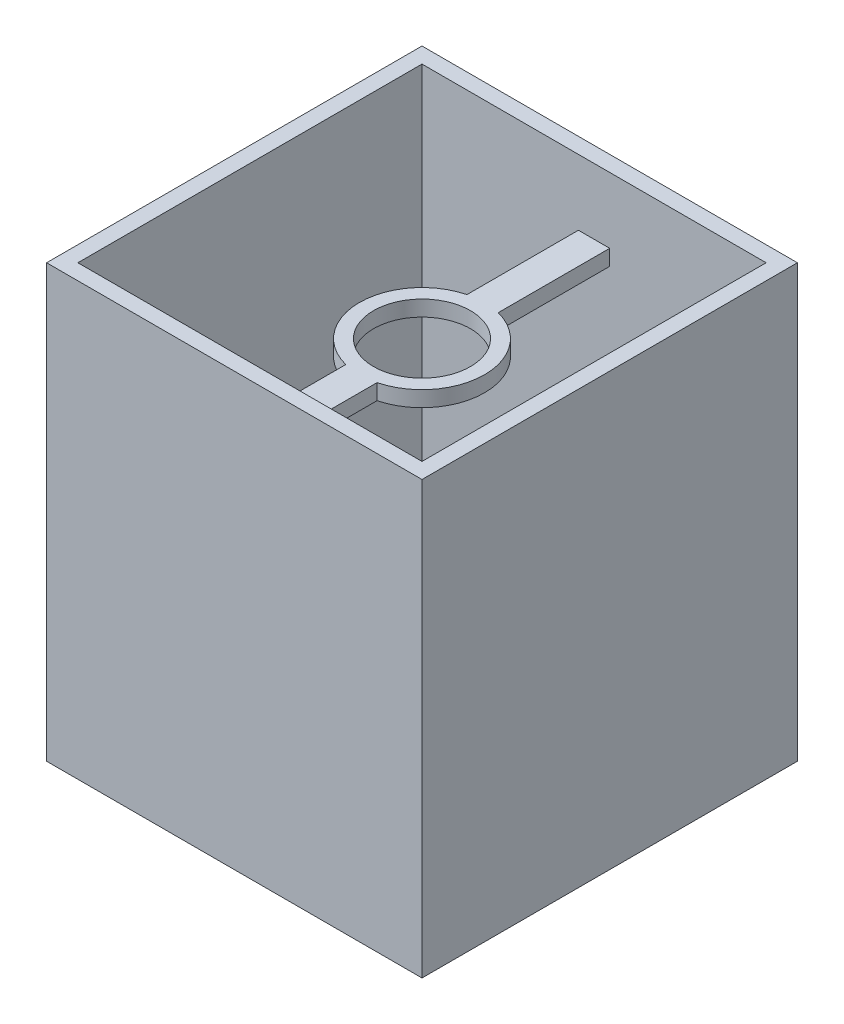
SolidWorks part; units mm, degrees
material "ABS"
ref_plane "Front Plane" through (0, 0, 0) normal (0, 0, 1) x (1, 0, 0)
ref_plane "Top Plane" through (0, 0, 0) normal (0, 1, 0) x (1, 0, 0)
ref_plane "Right Plane" through (0, 0, 0) normal (1, 0, 0) x (0, 0, -1)
sketch "Sketch1" plane through (0, 0, 0) normal (0, 1, 0) x (1, 0, 0)
  line L1 (30, -30) -> (-30, -30)
  line L2 (30, -30) -> (30, 30)
  line L3 (30, 30) -> (-30, 30)
  line L4 (-30, -30) -> (-30, 30)
  line L5 (30, -30) -> (-30, 30) construction
  line L6 (30, 30) -> (-30, -30) construction
  point P0 (0, 0)
  dimension "D1" = 60
  dimension "D2" = 60
extrude "Boss-Extrude1" add sketch "Sketch1" along normal blind 69
sketch "Sketch2" plane through (0, 69, 0) normal (0, 1, 0) x (1, 0, 0)
  line L1 (27.5, -27.5) -> (-27.5, -27.5)
  line L2 (27.5, -27.5) -> (27.5, 27.5)
  line L3 (27.5, 27.5) -> (-27.5, 27.5)
  line L4 (-27.5, -27.5) -> (-27.5, 27.5)
  line L5 (27.5, -27.5) -> (-27.5, 27.5) construction
  line L6 (27.5, 27.5) -> (-27.5, -27.5) construction
  point P0 (0, 0)
  dimension "D1" = 55
  dimension "D2" = 55
extrude "Cut-Extrude1" cut sketch "Sketch2" against normal blind 66.5
sketch "shaft axis" plane through (0, 0, 0) normal (0, 0, 1) x (1, 0, 0)
  line L1 (0, 2.5) -> (0, 81.7337)
  line L2 (27.5, 2.5) -> (-27.5, 2.5) construction
sketch "motor axis" plane through (0, 0, 0) normal (0, 0, 1) x (1, 0, 0)
  line L0 (3.5, 2.5) -> (3.5, 81.7337)
  line L1 (27.5, 2.5) -> (-27.5, 2.5) construction
  line L2 (0, 2.5) -> (0, 81.7337) construction
  dimension "D1" = 3.5
sketch "Sketch3" plane through (0, 2.5, 0) normal (0, 1, 0) x (1, 0, 0)
  line L0 (-27.5, -27.5) -> (27.5, -27.5) construction
  circle A0 centre (16.36, 2.5) radius 1.5
  circle A1 centre (16.36, -2.5) radius 1.5
  point P0 (16.36, 2.5)
  point P2 (16.36, -2.5)
  dimension "D1" = 25
  dimension "D2" = 5
  dimension "D3" = 3
  dimension "D4" = 16.36
extrude "Cut-Extrude2" cut sketch "Sketch3" against normal blind 1.875
thread "Thread4" pitch 0.5 method cut profile "Thread Profile5" start angle 0, offset 0, length 0, pitch 0.5, diameter 3
ref_plane "Plane5" through (14.86, 2.5, -2.5) normal (0, 0, 1) x (-1, 0, 0)
sketch "Thread Profile5" plane through (14.86, 2.5, -2.5) normal (0, 0, 1) x (-1, 0, 0)
  line L0 (0, 0) -> (0, 0.5) construction
  line L1 (0, 0) -> (0.2706, 0.1562)
  line L2 (0.2706, 0.1562) -> (0.2706, 0.2187)
  line L3 (0.2706, 0.2187) -> (0, 0.375)
  line L4 (0.2706, 0.1875) -> (0, 0.1875) construction
  line L11 (0, 0) -> (0, 0.375)
  point P2 (0, 0)
  dimension "Pitch" = 0.5
  dimension "Profile_Angle" = 60
  dimension "Profile_Land" = 0.0625
  dimension "Profile_Height" = 0.2706
thread "Thread5" pitch 0.5 method cut profile "Thread Profile6" start angle 0, offset 0, length 0, pitch 0.5, diameter 3
ref_plane "Plane6" through (14.86, 2.5, 2.5) normal (0, 0, 1) x (-1, 0, 0)
sketch "Thread Profile6" plane through (14.86, 2.5, 2.5) normal (0, 0, 1) x (-1, 0, 0)
  line L0 (0, 0) -> (0, 0.5) construction
  line L1 (0, 0) -> (0.2706, 0.1562)
  line L2 (0.2706, 0.1562) -> (0.2706, 0.2187)
  line L3 (0.2706, 0.2187) -> (0, 0.375)
  line L4 (0.2706, 0.1875) -> (0, 0.1875) construction
  line L11 (0, 0) -> (0, 0.375)
  point P2 (0, 0)
  dimension "Pitch" = 0.5
  dimension "Profile_Angle" = 60
  dimension "Profile_Land" = 0.0625
  dimension "Profile_Height" = 0.2706
ref_plane "Plane7" through (0, 58.5, 0) normal (0, 1, 0) x (1, 0, 0)
sketch "Sketch6" plane through (0, 58.5, 0) normal (0, 1, 0) x (1, 0, 0)
  line L0 (0, -27.5) -> (0, 27.5) construction
  line L1 (-27.5, -27.5) -> (27.5, -27.5) construction
  line L2 (27.5, 27.5) -> (-27.5, 27.5) construction
  line L3 (2.5, 27.5) -> (2.5, 9.6825)
  line L4 (27.5, 27.5) -> (-27.5, 27.5) construction
  line L5 (-2.5, 27.5) -> (-2.5, 9.6825)
  line L6 (-33, 0) -> (33, 0) construction
  line L7 (-2.5, -27.5) -> (-2.5, -9.6825)
  line L8 (2.5, -27.5) -> (2.5, -9.6825)
  line L9 (-2.5, 27.5) -> (2.5, 27.5)
  line L10 (-2.5, -27.5) -> (2.5, -27.5)
  circle A0 centre (0, 0) radius 7.75
  circle A1 centre (0, 0) radius 10
  dimension "D1" = 15.5
  dimension "D2" = 20
  dimension "D3" = 5
extrude "Boss-Extrude2" add sketch "Sketch6" against normal blind 2.5 contours L0 A1 L3 L9 | A1 L0 L9 L5 | A1 L0 A0 | L0 A1 A0 | L0 L10 L8 A1 | L10 L0 A1 L7 region at (-1.2537, 58.5, 18.6972) region at (1.2537, 58.5, 18.6972) region at (-1.2319, 58.5, 9.6985) region at (0.2236, 58.5, 8.875) region at (-1.2537, 58.5, -18.6972) region at (1.2537, 58.5, -18.6972)
